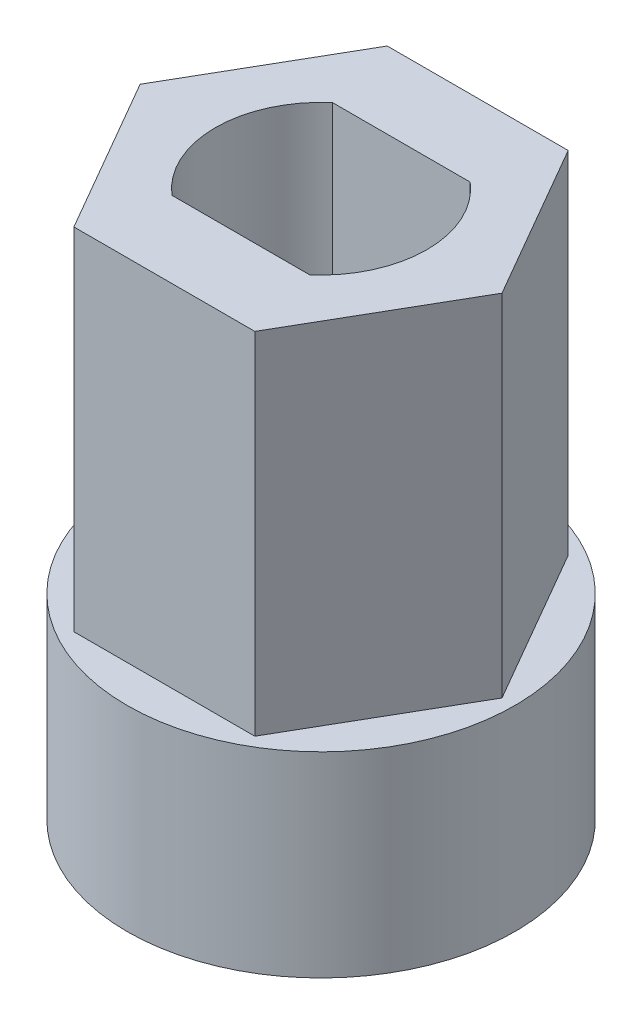
SolidWorks part; units mm, degrees
material "PLA"
ref_plane "Front Plane" through (0, 0, 0) normal (0, 0, 1) x (1, 0, 0)
ref_plane "Top Plane" through (0, 0, 0) normal (0, 1, 0) x (1, 0, 0)
ref_plane "Right Plane" through (0, 0, 0) normal (1, 0, 0) x (0, 0, -1)
sketch "Sketch1" plane through (0, 0, 0) normal (0, 1, 0) x (1, 0, 0)
  line L0 (-1.7571, 2.05) -> (1.7571, 2.05)
  line L1 (-1.7571, -2.05) -> (1.7571, -2.05)
  line L2 (0, 0) -> (2.45, 0) construction
  line L4 (2.3094, 4) -> (-2.3094, 4)
  line L5 (-2.3094, 4) -> (-4.6188, 0)
  line L6 (-4.6188, 0) -> (-2.3094, -4)
  line L7 (-2.3094, -4) -> (2.3094, -4)
  line L8 (2.3094, -4) -> (4.6188, 0)
  line L9 (4.6188, 0) -> (2.3094, 4)
  arc A0 (-1.7571, 2.05) -> (-1.7571, -2.05) centre (0, 0) ccw
  circle A2 centre (0, 0) radius 4 construction
  circle A3 centre (0, 0) radius 4.95
  arc A4 (1.7571, 2.05) -> (-1.7571, 2.05) centre (0, 0) ccw construction
  arc A5 (1.7571, -2.05) -> (1.7571, 2.05) centre (0, 0) ccw
  arc A6 (-1.7571, -2.05) -> (1.7571, -2.05) centre (0, 0) ccw construction
  dimension "D1" = 5.4
  dimension "D4" = 9.9
  dimension "D2" = 4.1
  dimension "D3" = 8
extrude "Boss-Extrude1" add sketch "Sketch1" along normal blind 8.95 contours L8 L9 L4 L5 L6 L7 A0 region at (3.3583, 0, -1.9389)
extrude "Boss-Extrude2" add sketch "Sketch1<3>" against normal blind 5 contours A3 L9 L8 L7 L6 L5 L4 | L8 L9 L4 L5 L6 L7 A5 L1 A0 L0 region at (3.3583, 0, -1.9389) region at (-4.81, 0, 0)
sketch "Sketch1<3>" plane through (0, 0, 0) normal (0, 1, 0) x (1, 0, 0) same geometry as "Sketch1"
